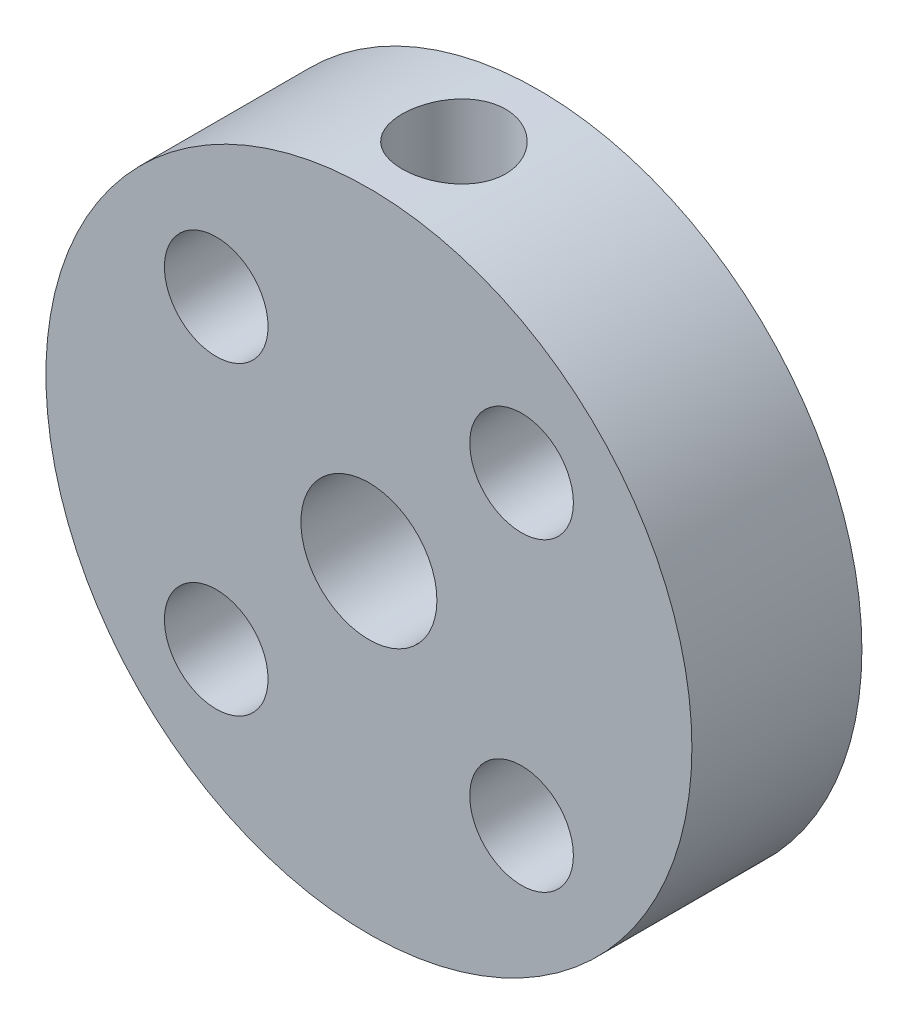
SolidWorks part; units mm, degrees
ref_plane "Front Plane" through (0, 0, 0) normal (0, 0, 1) x (1, 0, 0)
ref_plane "Top Plane" through (0, 0, 0) normal (0, 1, 0) x (1, 0, 0)
ref_plane "Right Plane" through (0, 0, 0) normal (1, 0, 0) x (0, 0, -1)
sketch "Sketch1" plane through (0, 0, 0) normal (0, 0, 1) x (1, 0, 0)
  line L0 (0, 0) -> (4.4901, -4.4901) construction
  line L1 (0, 0) -> (9.5, 0) construction
  circle A0 centre (0, 0) radius 9.5
  circle A1 centre (4.4901, -4.4901) radius 1.524
  circle A2 centre (-4.4901, -4.4901) radius 1.524
  circle A3 centre (-4.4901, 4.4901) radius 1.524
  circle A4 centre (4.4901, 4.4901) radius 1.524
  circle A5 centre (0, 0) radius 2
  point P13 (0, 0)
  point P17 (0, 0)
  dimension "D1" = 19
  dimension "D2" = 3.048
  dimension "D5" = 4
  dimension "D6" = 4
  dimension "D3" = 6.35
  dimension "D4" = 45
extrude "Boss-Extrude1" add sketch "Sketch1" along normal blind 5
ref_plane "Plane1" through (0, 2.9661, 0) normal (0, 1, 0) x (1, 0, 0)
sketch "Sketch3" plane through (0, 2.9661, 0) normal (0, 1, 0) x (1, 0, 0)
  line L0 (2, 0) -> (-2, 0) construction
  circle A0 centre (0, -2.5) radius 1.524
  dimension "D1" = 3.048
  dimension "D2" = 2.5
extrude "Cut-Extrude1" cut sketch "Sketch3" against normal up to surface and the other way up to surface up to face at (2, 0, 5) other way up to face at (9.5, 0, 5)
